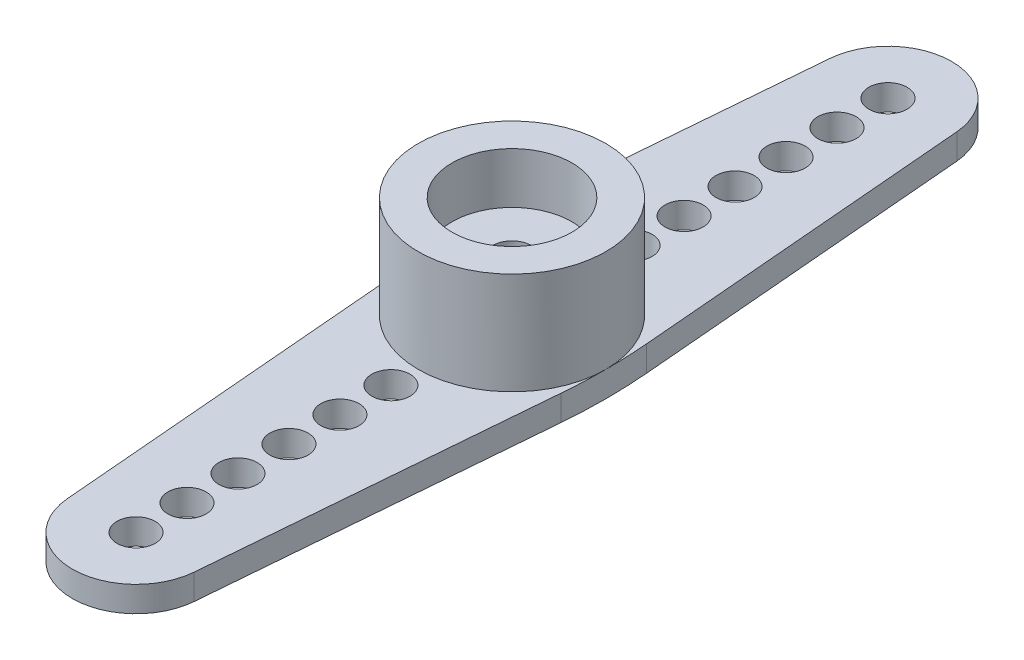
SolidWorks part; units mm, degrees
ref_plane "Front Plane" through (0, 0, 0) normal (0, 0, 1) x (1, 0, 0)
ref_plane "Top Plane" through (0, 0, 0) normal (0, 1, 0) x (1, 0, 0)
ref_plane "Right Plane" through (0, 0, 0) normal (1, 0, 0) x (0, 0, -1)
sketch "Sketch1" plane through (0, 0, 0) normal (0, 1, 0) x (1, 0, 0)
  line L0 (0, -14.75) -> (0, 14.75) construction
  line L1 (-2.5, -14.75) -> (-2.5, 14.75) construction
  line L2 (2.5, -14.75) -> (2.5, 14.75) construction
  line L3 (-2.4912, 14.9596) -> (-3.6089, 1.677)
  line L4 (-3.6089, -1.677) -> (-2.4912, -14.9596)
  line L5 (0, 0) -> (0, -19.6174) construction
  line L6 (3.6089, -1.677) -> (2.4912, -14.9596)
  line L7 (2.4912, 14.9596) -> (3.6089, 1.677)
  line L8 (0, 0) -> (20.4602, 0) construction
  arc A0 (-2.5, -14.75) -> (2.5, -14.75) centre (0, -14.75) ccw construction
  arc A1 (2.5, 14.75) -> (-2.5, 14.75) centre (0, 14.75) ccw construction
  arc A2 (-2.4912, 14.9596) -> (2.4912, 14.9596) centre (0, 14.75) cw
  arc A3 (-2.4912, -14.9596) -> (2.4912, -14.9596) centre (0, -14.75) ccw
  circle A4 centre (0, 14.75) radius 0.75
  arc A5 (3.6089, -1.677) -> (3.6089, 1.677) centre (-16.3207, 0) ccw
  arc A6 (-3.6089, 1.677) -> (-3.6089, -1.677) centre (16.3207, 0) ccw
  circle A7 centre (0, 0) radius 3.6793 construction
  circle A8 centre (0, 12.75) radius 0.75
  circle A9 centre (0, 10.75) radius 0.75
  circle A10 centre (0, 8.75) radius 0.75
  circle A11 centre (0, 6.75) radius 0.75
  circle A12 centre (0, 4.75) radius 0.75
  circle A13 centre (0, 0) radius 0.75
  circle A14 centre (0, -4.75) radius 0.75
  circle A15 centre (0, -6.75) radius 0.75
  circle A16 centre (0, -8.75) radius 0.75
  circle A17 centre (0, -10.75) radius 0.75
  circle A18 centre (0, -12.75) radius 0.75
  circle A19 centre (0, -14.75) radius 0.75
  point P2 (0, 0)
  point P21 (3.75, 0)
  point P24 (-3.75, 0)
  dimension "D1" = 2.5
  dimension "D4" = 1.5
  dimension "D5" = 20
  dimension "D2" = 29.5
  dimension "D3" = 3.75
  dimension "D7" = 2
  dimension "D6" = 6
extrude "Boss-Extrude1" add sketch "Sketch1" along normal blind 1
sketch "Sketch2" plane through (0, 0, 0) normal (0, -1, 0) x (1, 0, 0)
  circle A0 centre (0, 0) radius 3.6793 construction
  circle A1 centre (0, 0) radius 3.6793
  circle A2 centre (0, 0) radius 1.5
  dimension "D1" = 3
extrude "Boss-Extrude2" add sketch "Sketch2" against normal blind 5 contours A1
extrude "Cut-Extrude1" cut sketch "Sketch2<3>" against normal blind 0.5 contours A2
sketch "Sketch2<3>" plane through (0, 0, 0) normal (0, -1, 0) x (1, 0, 0) same geometry as "Sketch2"
extrude "Cut-Extrude2" cut sketch "Sketch1<2>" along normal through all contours A13
sketch "Sketch1<2>" plane through (0, 0, 0) normal (0, 1, 0) x (1, 0, 0) same geometry as "Sketch1"
sketch "Sketch3" plane through (0, 5, 0) normal (0, 1, 0) x (1, 0, 0)
  circle A0 centre (0, 0) radius 2.355
  dimension "D1" = 4.71
extrude "Cut-Extrude3" cut sketch "Sketch3" against normal blind 2
